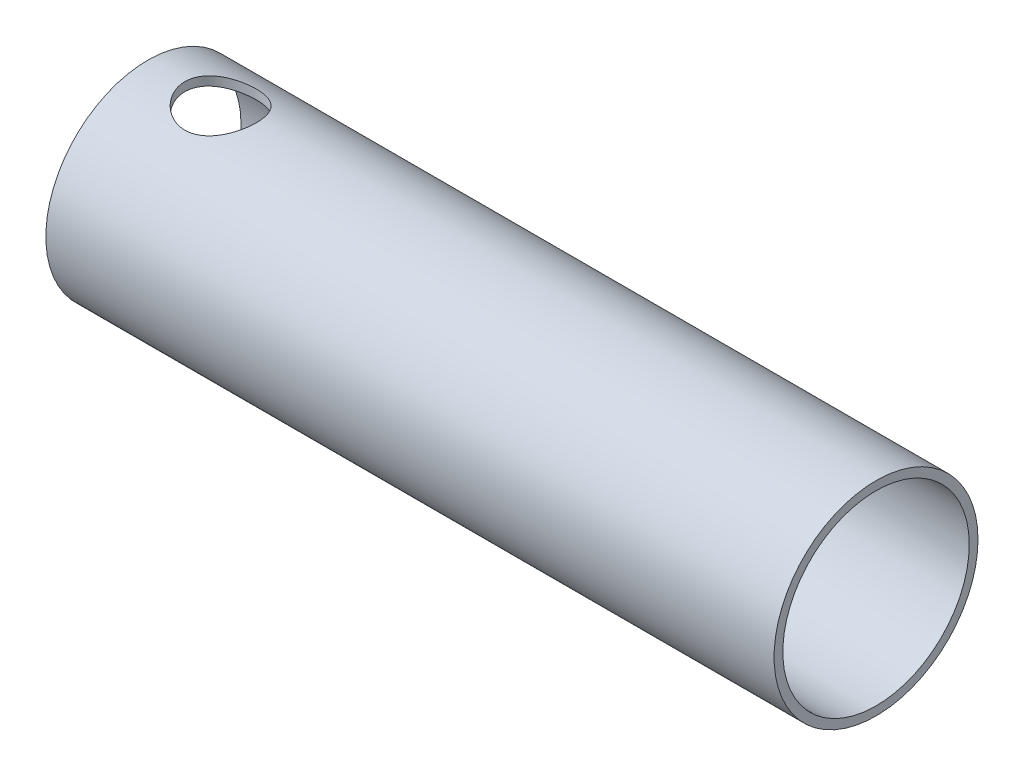
SolidWorks part; units mm, degrees
ref_plane "Front Plane" through (0, 0, 0) normal (0, 0, 1) x (1, 0, 0)
ref_plane "Top Plane" through (0, 0, 0) normal (0, 1, 0) x (1, 0, 0)
ref_plane "Right Plane" through (0, 0, 0) normal (1, 0, 0) x (0, 0, -1)
sketch "Sketch3" plane through (0, 0, 0) normal (1, 0, 0) x (0, 0, -1)
  circle A0 centre (0, 0) radius 32
  circle A1 centre (0, 0) radius 35
  dimension "D1" = 64
  dimension "D2" = 70
extrude "Boss-Extrude1" add sketch "Sketch3" along normal blind 250
sketch "Sketch4" plane through (0, 0, 0) normal (0, 1, 0) x (1, 0, 0)
  circle A0 centre (25, 0) radius 12.25
  point P2 (0, 0)
  dimension "D2" = 24.5
  dimension "D1" = 25
extrude "Cut-Extrude1" cut sketch "Sketch4" against normal through all both and the other way through all
